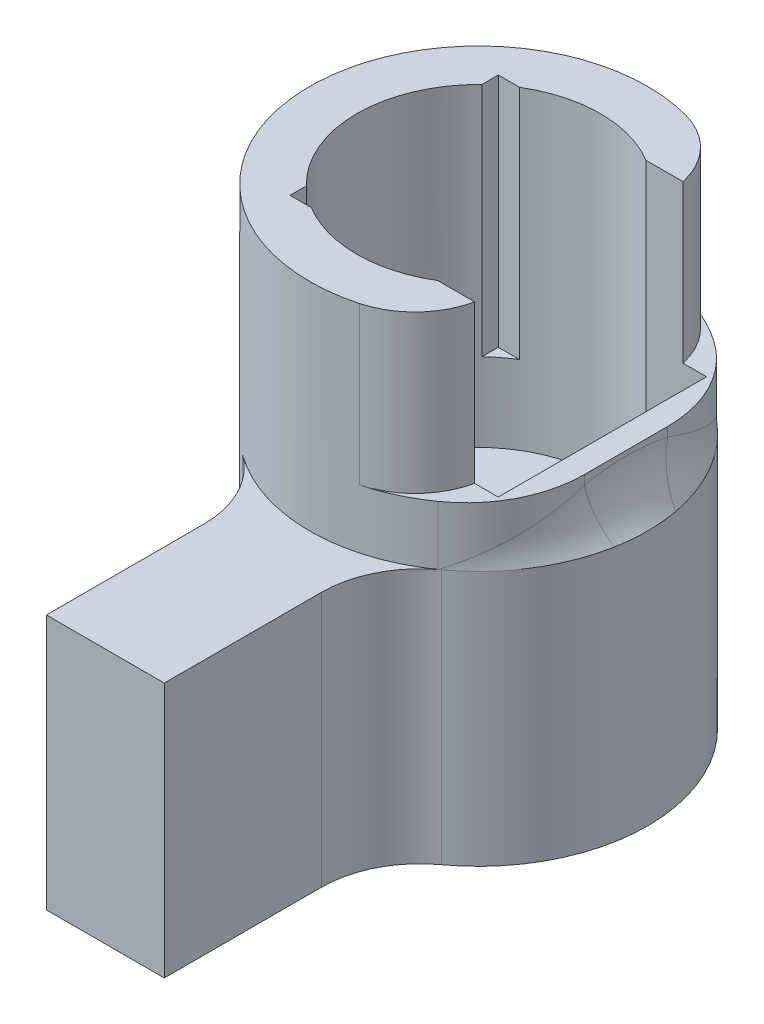
SolidWorks part; units mm, degrees
ref_plane "Спереди" through (0, 0, 0) normal (0, 0, 1) x (1, 0, 0)
ref_plane "Сверху" through (0, 0, 0) normal (0, 1, 0) x (1, 0, 0)
ref_plane "Справа" through (0, 0, 0) normal (1, 0, 0) x (0, 0, -1)
sketch "Sketch1" plane through (0, 0, 0) normal (0, 1, 0) x (1, 0, 0)
  circle A0 centre (0, 0) radius 4.3
  circle A1 centre (0, 0) radius 1.6
  dimension "D1" = 8.6
  dimension "D2" = 3.2
extrude "Boss-Extrude1" add sketch "Sketch1" along normal blind 12
sketch "Sketch2" plane through (0, 12, 0) normal (0, 1, 0) x (1, 0, 0)
  circle A0 centre (0, 0) radius 3.1
  dimension "D1" = 6.2
extrude "Cut-Extrude1" cut sketch "Sketch2" against normal blind 8
sketch "Sketch3" plane through (0, 12, 0) normal (0, 1, 0) x (1, 0, 0)
  line L0 (-4.3, 0) -> (4.3, 0) construction
  line L1 (3.15, -2.65) -> (-2.15, -2.65)
  line L2 (3.15, -2.65) -> (3.15, 2.65)
  line L3 (3.15, 2.65) -> (-2.15, 2.65)
  line L4 (-2.15, -2.65) -> (-2.15, 2.65)
  line L5 (3.15, -2.65) -> (-2.15, 2.65) construction
  line L6 (3.15, 2.65) -> (-2.15, -2.65) construction
  circle A0 centre (0, 0) radius 4.3 construction
  point P0 (0.5, 0)
  point P6 (0, 0)
  dimension "D1" = 5.3
  dimension "D2" = 5.3
  dimension "D3" = 0.5
extrude "Cut-Extrude2" cut sketch "Sketch3" against normal blind 6
sketch "Sketch6" plane through (0, 0, 0) normal (0, -1, 0) x (1, 0, 0)
  line L0 (-4.3, 0) -> (4.3, 0) construction
  line L1 (0, 0) -> (0, 10) construction
  line L3 (1.5, 9.5) -> (-1.5, 9.5)
  line L4 (1.5, 9.5) -> (1.5, 3.5)
  line L5 (1.5, 3.5) -> (-1.5, 3.5)
  line L6 (-1.5, 9.5) -> (-1.5, 3.5)
  line L7 (1.5, 9.5) -> (-1.5, 3.5) construction
  line L8 (1.5, 3.5) -> (-1.5, 9.5) construction
  circle A0 centre (0, 0) radius 4.3 construction
  point P8 (0, 6.5)
  dimension "D1" = 10
  dimension "D2" = 3.5
  dimension "D3" = 6
  dimension "D4" = 3
extrude "Boss-Extrude3" add sketch "Sketch6" against normal blind 6.5
sketch "Sketch7" plane through (0, 12, 0) normal (0, 1, 0) x (1, 0, 0)
  line L0 (-3.75, 2.1042) -> (-3.75, -2.1042) construction
  line L1 (3.75, 2.1042) -> (3.75, -2.1042) construction
  line L2 (-2.15, 2.65) -> (-2.15, 2.2333) construction
  line L4 (3.75, 2.1042) -> (3.75, -2.1042)
  circle A0 centre (0, 0) radius 4.3 construction
  arc A2 (3.75, 2.1042) -> (3.75, -2.1042) centre (0.1236, 0) cw
  dimension "D1" = 7.5
extrude "Cut-Extrude4" cut sketch "Sketch7" against normal blind 5.5
fillet "Fillet1" radius 3 2 edges at (3.75, 9.25, 2.1042) (3.75, 9.25, -2.1042)
fillet "Fillet2" radius 2 3 edges at (3.4139, 6.5, -2.4416) (3.4139, 6.5, 2.4416) (3.75, 6.5, 0)
sketch "Sketch9" plane through (0, 12, 0) normal (0, 1, 0) x (1, 0, 0)
  line L0 (2.55, 3.4618) -> (2.55, -3.4618)
  line L2 (3.75, 1.0618) -> (3.75, -1.0618)
  arc A0 (3.75, 1.0618) -> (2.4808, 3.5122) centre (0.75, 1.0618) ccw construction
  arc A1 (2.4808, -3.5122) -> (3.75, -1.0618) centre (0.75, -1.0618) ccw construction
  arc A2 (3.75, 1.0618) -> (2.55, 3.4618) centre (0.75, 1.0618) ccw
  arc A3 (3.75, -1.0618) -> (2.55, -3.4618) centre (0.75, -1.0618) cw
  dimension "D1" = 1.2
extrude "Cut-Extrude6" cut sketch "Sketch9" against normal blind 4
fillet "Fillet4" radius 2.5 2 edges at (-1.5, 3.25, 4.0299) (1.5, 3.25, 4.0299)
fillet "Fillet5" radius 2 2 edges at (2.55, 10, -3.4618) (2.55, 10, 3.4618)
